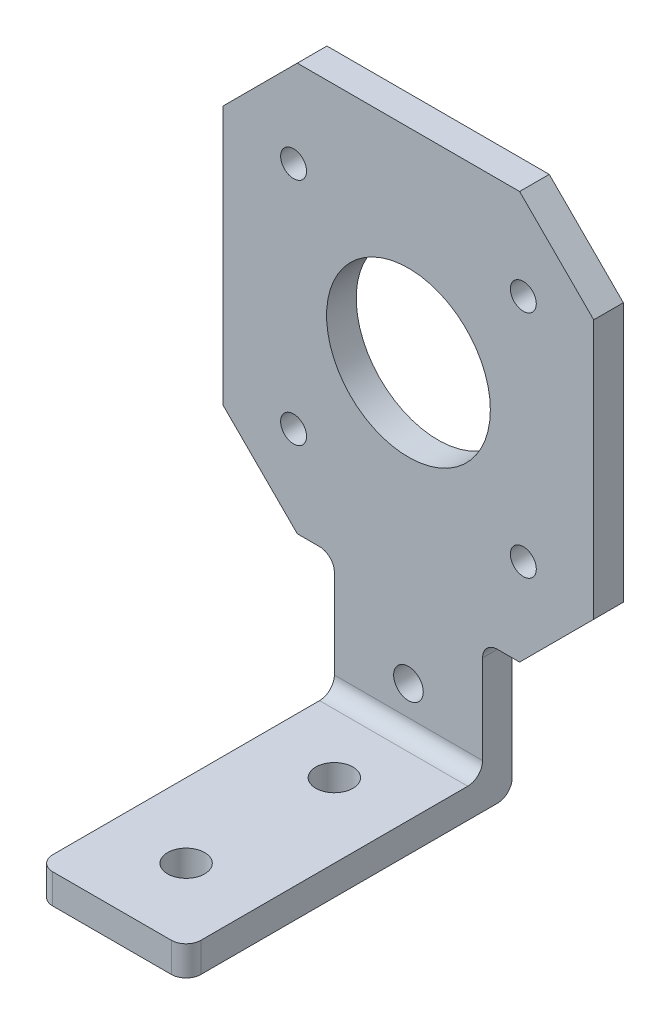
SolidWorks part; units mm, degrees
material "PLA"
ref_plane "Piano frontale" through (0, 0, 0) normal (0, 0, 1) x (1, 0, 0)
ref_plane "Piano superiore" through (0, 0, 0) normal (0, 1, 0) x (1, 0, 0)
ref_plane "Piano destro" through (0, 0, 0) normal (1, 0, 0) x (0, 0, -1)
sketch "Schizzo1" plane through (0, 0, 0) normal (0, 0, 1) x (1, 0, 0)
  line L5 (0, 0) -> (0, -67.5867) construction
  line L6 (-25, -27.5) -> (-10, -27.5)
  line L10 (-25, -27.5) -> (-25, 27.5)
  line L11 (-15.5, 15.5) -> (15.5, 15.5) construction
  line L12 (-15.5, 15.5) -> (-15.5, -15.5) construction
  line L13 (-15.5, -15.5) -> (15.5, -15.5) construction
  line L14 (15.5, 15.5) -> (15.5, -15.5) construction
  line L15 (-15.5, 15.5) -> (15.5, -15.5) construction
  line L16 (-15.5, -15.5) -> (15.5, 15.5) construction
  line L17 (-25, 27.5) -> (25, 27.5)
  line L18 (25, -27.5) -> (25, 27.5)
  line L22 (-25, -27.5) -> (25, 27.5) construction
  line L27 (-25, 27.5) -> (25, -27.5) construction
  line L29 (-10, -47.5) -> (10, -47.5)
  line L31 (-10, -47.5) -> (-10, -27.5)
  line L33 (10, -47.5) -> (10, -27.5)
  line L34 (-10, -47.5) -> (10, -27.5) construction
  line L35 (-10, -27.5) -> (10, -47.5) construction
  line L36 (10, -27.5) -> (25, -27.5)
  circle A0 centre (-15.5, 15.5) radius 1.75
  circle A1 centre (15.5, 15.5) radius 1.75
  circle A2 centre (15.5, -15.5) radius 1.75
  circle A3 centre (-15.5, -15.5) radius 1.75
  circle A4 centre (0, 0) radius 11.05
  point P4 (0, -37.5)
  point P14 (0, 0)
  dimension "D10" = 3.5
  dimension "D11" = 22.1
  dimension "D2" = 50
  dimension "D4" = 20
  dimension "D3" = 55
  dimension "D8" = 31
  dimension "D5" = 20
extrude "Estrusione-Estrusione1" add sketch "Schizzo1" along normal blind 4
sketch "Schizzo14" plane through (0, 0, 4) normal (0, 0, 1) x (1, 0, 0)
  line L0 (10, -47.5) -> (10, -27.5) construction
  line L1 (-10, -47.5) -> (10, -47.5)
  line L2 (-10, -47.5) -> (-10, -43.5)
  line L3 (-10, -43.5) -> (10, -43.5)
  line L4 (10, -47.5) -> (10, -43.5)
  dimension "D1" = 4
extrude "Estrusione-Estrusione2" add sketch "Schizzo14" along normal blind 40
sketch "Schizzo15" plane through (0, 0, 4) normal (0, 0, 1) x (1, 0, 0)
  line L1 (10, -43.5) -> (10, -27.5) construction
  line L2 (-25, -27.5) -> (-10, -27.5) construction
  circle A0 centre (0, -37.5) radius 2
  dimension "D1" = 4
  dimension "D2" = 10
  dimension "D3" = 10
extrude "Taglio-Estrusione1" cut sketch "Schizzo15" against normal through all
sketch "Schizzo16" plane through (0, -43.5, 0) normal (0, 1, 0) x (1, 0, 0)
  line L0 (0, -4) -> (0, -44) construction
  line L1 (10, -4) -> (-10, -4) construction
  line L2 (10, -44) -> (-10, -44) construction
  circle A1 centre (0, -34) radius 2.5
  circle A2 centre (0, -14) radius 2.5
  dimension "D1" = 10
  dimension "D2" = 5
  dimension "D3" = 5
  dimension "D4" = 10
extrude "Taglio-Estrusione2" cut sketch "Schizzo16" against normal through all
chamfer "Smusso1" distance 10 angle 45 4 edges at (25, 27.5, 2) (25, -27.5, 2) (-25, -27.5, 2) (-25, 27.5, 2)
fillet "Raccordo1" radius 2 6 edges at (0, -47.5, 0) (10, -45.5, 44) (-10, -45.5, 44) (-10, -27.5, 2) (10, -27.5, 2) (0, -43.5, 4)
